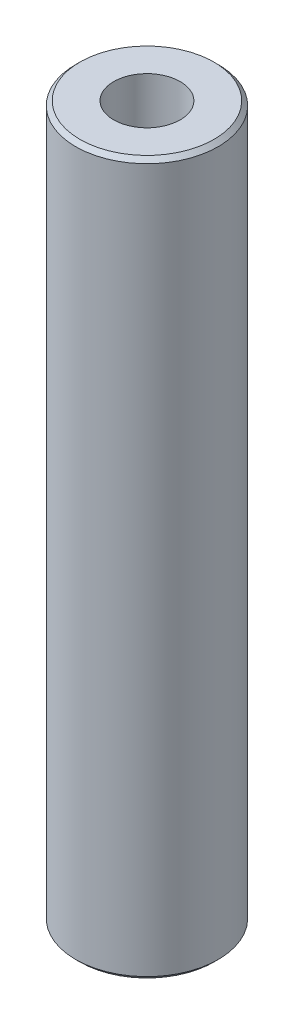
SolidWorks part; units mm, degrees
ref_plane "Front Plane" through (0, 0, 0) normal (0, 0, 1) x (1, 0, 0)
ref_plane "Top Plane" through (0, 0, 0) normal (0, 1, 0) x (1, 0, 0)
ref_plane "Right Plane" through (0, 0, 0) normal (1, 0, 0) x (0, 0, -1)
sketch "Sketch1" plane through (0, 0, 0) normal (0, 1, 0) x (1, 0, 0)
  circle A0 centre (0, 0) radius 60
  dimension "SHAFT_OD" = 120
extrude "Boss-Extrude1" add sketch "Sketch1" along normal blind 600
sketch "Sketch2" plane through (0, 0, 0) normal (0, 1, 0) x (1, 0, 0)
  circle A0 centre (0, 0) radius 27.9818
  dimension "BORE_D" = 55.9636
extrude "Cut-Extrude1" cut sketch "Sketch2" along normal through all
chamfer "Chamfer1" distance 3.5475 angle 45 2 edges at (0, 600, 60) (0, 0, 60)
